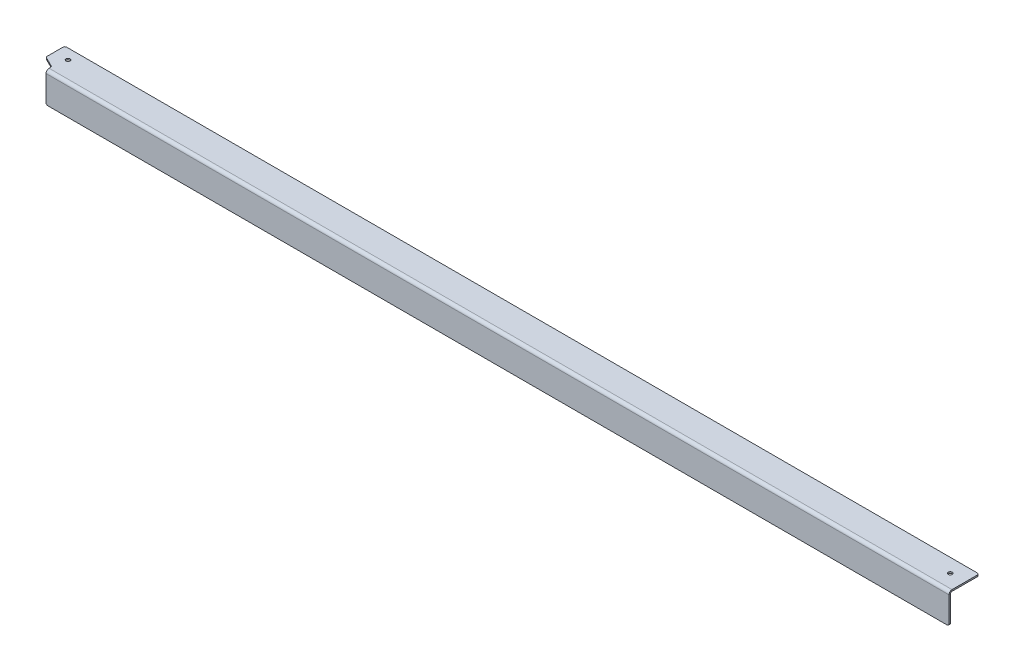
SolidWorks part; units mm, degrees
note: The reader was unsure of these and kept them because the rebuilt part matched: flange length of "Edge-Flange1".
material "5052-H36"
ref_plane "Front Plane" through (0, 0, 0) normal (0, 0, 1) x (1, 0, 0)
ref_plane "Top Plane" through (0, 0, 0) normal (0, 1, 0) x (1, 0, 0)
ref_plane "Right Plane" through (0, 0, 0) normal (1, 0, 0) x (0, 0, -1)
sketch "Sketch2" plane through (0, 0, 0) normal (0, 1, 0) x (1, 0, 0)
  line L1 (0, 0) -> (1524, 0)
  line L2 (0, 0) -> (0, 9.525)
  line L3 (-19.05, 50.8) -> (1524, 50.8)
  line L4 (1524, 0) -> (1524, 50.8)
  line L5 (-19.05, 50.8) -> (-19.05, 19.05)
  line L6 (-19.05, 19.05) -> (0, 9.525)
  dimension "D1" = 1524
  dimension "D2" = 1543.05
  dimension "D3" = 9.525
  dimension "D4" = 50.8
  dimension "D5" = 31.75
base flange "Base-Flange1" sketch "Sketch2" thickness 2.5908 reverse thickness direction no parameters "D1"=2.54
edge flange "Edge-Flange1" sketch "Sketch9" flange angle 90 flange length 50.8 bend radius 2.54 thickness 2.5908 relief rectangular parameters "D6"=10
sketch "Sketch9" plane through (0, -2.5908, 0) normal (0, 0, 1) x (-1, 0, 0)
  line L0 (0, 0) -> (-1524, 0) construction
  line L1 (0, 0) -> (-1524, 0)
  line L2 (-1524, 0) -> (-1524, 48.2092)
  line L3 (-1524, 48.2092) -> (0, 48.2092)
  line L4 (0, 48.2092) -> (0, 0)
bend "EdgeBend1" bend radius 2.54 bend angle 90 parameters "D5"=1
hole_wizard "17/64 (0.26563) Diameter Hole1" positions "Sketch10" profile "Sketch11" hole size "17/64" standard "ANSI Inch" end condition through all
sketch "Sketch10" plane through (0, 0, 0) normal (0, 1, 0) x (1, 0, 0)
  line L0 (0, 0) -> (1524, 0) construction
  line L1 (1524, 5.1308) -> (1524, 50.8) construction
  point P0 (1498.6, 27.305)
  dimension "D1" = 27.305
  dimension "D2" = 25.4
sketch "Sketch11" plane through (1498.6, 0, -27.305) normal (1, 0, 0) x (0, 0, 1)
  line L0 (0, 0) -> (0, 50.8)
  line L1 (0, 50.8) -> (3.3735, 50.8)
  line L2 (3.3735, 50.8) -> (3.3735, 0)
  line L5 (3.3735, 0) -> (0, 0)
  line L11 (0, -6.35) -> (0, 107.95) construction
  dimension "Thru Hole Dia." = 6.747
  dimension "Thru Hole Depth" = 50.8
fillet "Fillet1" radius 3.175 6 edges at (1524, -50.8, -1.2954) (1524, -1.2954, -50.8) (0, -50.8, -1.2954) (-19.05, -1.2954, -50.8) (-19.05, -1.2954, -19.05) (0, -1.2954, -9.525)
hole_wizard "17/64 (0.26563) Diameter Hole2" positions "Sketch13" profile "Sketch14" hole size "17/64" standard "ANSI Inch" end condition through all
sketch "Sketch13" plane through (0, 0, 0) normal (0, 1, 0) x (1, 0, 0)
  line L0 (0, 0) -> (1524, 0) construction
  line L1 (-19.05, 47.625) -> (-19.05, 21.0123) construction
  point P0 (3.81, 33.3375)
  dimension "D1" = 33.3375
  dimension "D2" = 22.86
sketch "Sketch14" plane through (3.81, 0, -33.3375) normal (1, 0, 0) x (0, 0, 1)
  line L0 (0, 0) -> (0, 50.8)
  line L1 (0, 50.8) -> (3.3735, 50.8)
  line L2 (3.3735, 50.8) -> (3.3735, 0)
  line L5 (3.3735, 0) -> (0, 0)
  line L11 (0, -6.35) -> (0, 107.95) construction
  dimension "Thru Hole Dia." = 6.747
  dimension "Thru Hole Depth" = 50.8
sketch "Bend-Lines1" [suppressed] plane through (0, 0, 0) normal (0, 1, 0) x (1, 0, 0)
sketch "Bounding-Box1" [suppressed] plane through (0, 0, 0) normal (0, 1, 0) x (1, 0, 0)
sheet metal parameters "Sheet-Metal1" thickness 2.5908 parameters "D1"=2.54
flat pattern "Flat-Pattern1" [suppressed]
sketch "Bend-Lines2" plane through (0, 0, 0) normal (0, 1, 0) x (1, 0, 0)
sketch3d "Bounding-Box2" [suppressed]
  line L0 (-1511.3, 63.5, 0) -> (0, 63.5, 0) construction
  line L1 (-1511.3, 0, 0) -> (0, 0, 0) construction
  line L2 (-1511.3, 63.5, 0) -> (-1511.3, 0, 0) construction
  line L3 (0, 63.5, 0) -> (0, 0, 0) construction
sheet metal parameters "Sheet-Metal2" thickness 2.5908 parameters "D1"=2.54
flat pattern "Flat-Pattern1"
sketch "Bend-Lines2" plane through (0, 0, 0) normal (0, 1, 0) x (1, 0, 0)
  line L0 (0, 2.1185) -> (1524, 2.1185) construction
  line L1 (0, 2.1185) -> (1524, 2.1185) construction
sketch3d "Bounding-Box2" [suppressed]
  line L0 (1524, 50.8, 0) -> (0, 50.8, 0) construction
  line L1 (1524, -46.563, 0) -> (0, -46.563, 0) construction
  line L2 (1524, 50.8, 0) -> (1524, -46.563, 0) construction
  line L3 (0, 50.8, 0) -> (0, -46.563, 0) construction
bend of the flat pattern "Flatten-<EdgeBend1>1"
sheet metal parameters "Sheet-Metal3" thickness 2.5908 parameters "D1"=2.54
flat pattern "Flat-Pattern1"
sketch "Bend-Lines2" plane through (0, 0, 0) normal (0, 1, 0) x (1, 0, 0)
  line L0 (0, 2.1185) -> (1524, 2.1185) construction
  line L1 (0, 2.1185) -> (1524, 2.1185) construction
sketch3d "Bounding-Box2" [suppressed]
  line L0 (1524, 50.8, 0) -> (-19.05, 50.8, 0) construction
  line L1 (1524, -46.563, 0) -> (-19.05, -46.563, 0) construction
  line L2 (1524, 50.8, 0) -> (1524, -46.563, 0) construction
  line L3 (-19.05, 50.8, 0) -> (-19.05, -46.563, 0) construction
bend of the flat pattern "Flatten-<EdgeBend1>1"
sheet metal parameters "Sheet-Metal5" thickness 2.5908 parameters "D1"=2.54
flat pattern "Flat-Pattern1"
sketch "Bend-Lines2" plane through (0, 0, 0) normal (0, 1, 0) x (1, 0, 0)
  line L0 (0, 2.1185) -> (1524, 2.1185) construction
  line L1 (0, 2.1185) -> (1524, 2.1185) construction
sketch3d "Bounding-Box2" [suppressed]
  line L0 (1524, 50.8, 0) -> (-19.05, 50.8, 0) construction
  line L1 (1524, -46.563, 0) -> (-19.05, -46.563, 0) construction
  line L2 (1524, 50.8, 0) -> (1524, -46.563, 0) construction
  line L3 (-19.05, 50.8, 0) -> (-19.05, -46.563, 0) construction
bend of the flat pattern "Flatten-<EdgeBend1>1"
